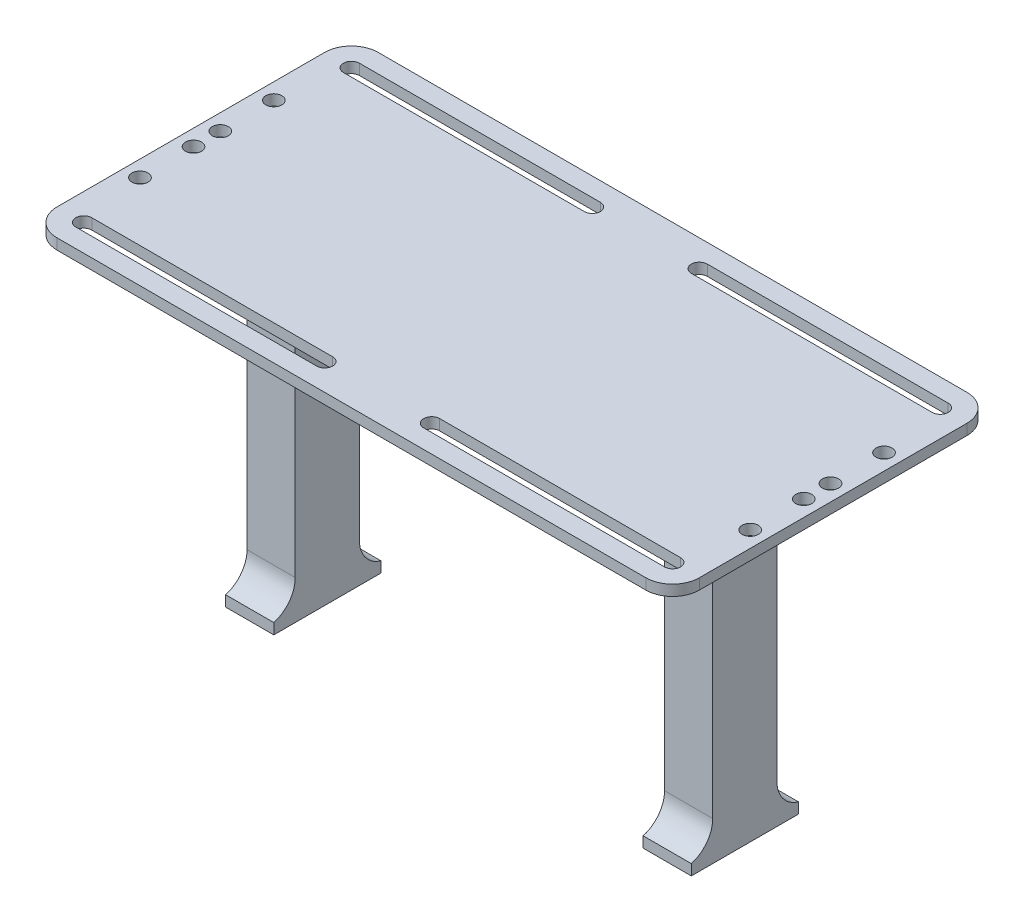
SolidWorks part; units mm, degrees
ref_plane "Front Plane" through (0, 0, 0) normal (0, 0, 1) x (1, 0, 0)
ref_plane "Top Plane" through (0, 0, 0) normal (0, 1, 0) x (1, 0, 0)
ref_plane "Right Plane" through (0, 0, 0) normal (1, 0, 0) x (0, 0, -1)
sketch "Sketch1" plane through (0, 0, 0) normal (0, 1, 0) x (1, 0, 0)
  line L0 (0, -1.9979) -> (0, 3.4727) construction
  line L1 (43.5, -6) -> (34.5, -6)
  line L2 (-43.5, 6) -> (-34.5, 6)
  line L3 (-43.5, 6) -> (-43.5, -6)
  line L4 (-43.5, -6) -> (-34.5, -6)
  line L5 (-34.5, 6) -> (-34.5, -6)
  line L6 (-43.5, 6) -> (-34.5, -6) construction
  line L7 (-43.5, -6) -> (-34.5, 6) construction
  line L8 (34.5, 6) -> (34.5, -6)
  line L9 (43.5, 6) -> (34.5, 6)
  line L10 (43.5, 6) -> (43.5, -6)
  circle A0 centre (-39, 0) radius 1.4
  circle A1 centre (39, 0) radius 1.4
  dimension "D1" = 2.8
  dimension "D2" = 78
  dimension "D3" = 9
  dimension "D4" = 12
extrude "Boss-Extrude1" add sketch "Sketch1" along normal blind 60 contours L3 L2 L5 L4 | L1 L8 L9 L10
sketch "Sketch2" plane through (0, 0, 0) normal (0, -1, 0) x (1, 0, 0)
  line L0 (0, 0) -> (0, 22.5272) construction
  line L1 (-43.5, 10) -> (-34.5, 10)
  line L2 (-43.5, 10) -> (-43.5, -10)
  line L3 (-43.5, -10) -> (-34.5, -10)
  line L4 (-34.5, 10) -> (-34.5, -10)
  line L5 (-34.5, -6) -> (-34.5, 6) construction
  line L6 (-43.5, -6) -> (-43.5, 6) construction
  line L7 (0, 0) -> (5.7315, 0) construction
  line L8 (43.5, -10) -> (34.5, -10)
  line L9 (34.5, 10) -> (34.5, -10)
  line L10 (43.5, 10) -> (34.5, 10)
  line L11 (43.5, 10) -> (43.5, -10)
  point P12 (-34.5, 0)
  dimension "D1" = 20
extrude "Boss-Extrude2" add sketch "Sketch2" along normal blind 2
sketch "Sketch3" plane through (0, -2, 0) normal (0, -1, 0) x (1, 0, 0)
  line L4 (-43.5, -6) -> (-34.5, -6)
  line L5 (-34.5, -6) -> (-34.5, 6)
  line L6 (-34.5, 6) -> (-43.5, 6)
  line L7 (-43.5, 6) -> (-43.5, -6)
  line L8 (-43.5, -6) -> (-34.5, -6)
  line L9 (-34.5, -6) -> (-34.5, 6)
  line L10 (-34.5, 6) -> (-43.5, 6)
  line L11 (-43.5, 6) -> (-43.5, -6)
  line L12 (43.5, 6) -> (34.5, 6)
  line L13 (34.5, 6) -> (34.5, -6)
  line L14 (34.5, -6) -> (43.5, -6)
  line L15 (43.5, -6) -> (43.5, 6)
  line L16 (43.5, 6) -> (34.5, 6)
  line L17 (34.5, 6) -> (34.5, -6)
  line L18 (34.5, -6) -> (43.5, -6)
  line L19 (43.5, -6) -> (43.5, 6)
  circle A1 centre (39, 0) radius 1.4
  circle A2 centre (39, 0) radius 1.4
  circle A3 centre (-39, 0) radius 1.4
  circle A4 centre (-39, 0) radius 1.4
  dimension "D1" = 0
  dimension "D2" = 0
  dimension "D3" = 0
  dimension "D4" = 0
extrude "Cut-Extrude1" cut sketch "Sketch3" against normal blind 6 contours A4 | A2
fillet "Fillet1" radius 5.5 2 edges at (-39, 0, -6) (-39, 0, 6)
fillet "Fillet2" radius 5.5 2 edges at (39, 0, -6) (39, 0, 6)
sketch "Sketch4" plane through (0, 60, 0) normal (0, 1, 0) x (1, 0, 0)
  line L0 (-60, 0) -> (60, 0) construction
  line L1 (-55, 30) -> (55, 30)
  line L2 (-60, 25) -> (-60, -25)
  line L3 (-55, -30) -> (55, -30)
  line L4 (60, 25) -> (60, -25)
  line L5 (-60, 30) -> (60, -30) construction
  line L6 (-60, -30) -> (60, 30) construction
  line L7 (0, -30) -> (0, 30) construction
  line L8 (55, 25) -> (10, 25) construction
  line L11 (55, 23.5) -> (10, 23.5)
  line L14 (-55, -25) -> (-10, -25) construction
  line L15 (-55, -23.5) -> (-10, -23.5)
  line L16 (-55, -26.5) -> (-10, -26.5)
  line L17 (55, 26.5) -> (10, 26.5)
  line L20 (-60, 30) -> (60, -30) construction
  line L21 (-60, -30) -> (60, 30) construction
  line L22 (-55, 30) -> (55, 30)
  line L23 (55, -25) -> (10, -25) construction
  line L26 (-55, 25) -> (-10, 25) construction
  line L27 (-55, 23.5) -> (-10, 23.5)
  line L28 (-55, 26.5) -> (-10, 26.5)
  line L29 (55, -23.5) -> (10, -23.5)
  line L30 (55, -26.5) -> (10, -26.5)
  arc A0 (55, 30) -> (60, 25) centre (55, 25) cw
  arc A1 (-60, -25) -> (-55, -30) centre (-55, -25) ccw
  arc A2 (-55, 30) -> (-60, 25) centre (-55, 25) ccw
  arc A3 (55, -30) -> (60, -25) centre (55, -25) ccw
  arc A8 (-55, -23.5) -> (-55, -26.5) centre (-55, -25) ccw
  arc A9 (-10, -26.5) -> (-10, -23.5) centre (-10, -25) ccw
  circle A10 centre (-57, -2.5) radius 1.5
  circle A11 centre (-57, -12.5) radius 1.5
  circle A16 centre (57, -12.5) radius 1.5
  circle A17 centre (57, -2.5) radius 1.5
  circle A18 centre (57, 2.5) radius 1.5
  circle A19 centre (57, 12.5) radius 1.5
  circle A22 centre (-57, 12.5) radius 1.5
  circle A23 centre (-57, 2.5) radius 1.5
  arc A24 (55, 30) -> (60, 25) centre (55, 25) cw
  arc A25 (-60, 25) -> (-55, 30) centre (-55, 25) cw
  arc A28 (-55, 23.5) -> (-55, 26.5) centre (-55, 25) cw
  arc A29 (-10, 26.5) -> (-10, 23.5) centre (-10, 25) cw
  circle A30 centre (-57, -22.5) radius 1.5
  arc A31 (55, 23.5) -> (55, 26.5) centre (55, 25) ccw
  arc A32 (10, 26.5) -> (10, 23.5) centre (10, 25) ccw
  arc A33 (55, -23.5) -> (55, -26.5) centre (55, -25) cw
  arc A34 (10, -26.5) -> (10, -23.5) centre (10, -25) cw
  point P0 (0, 0)
  point P22 (40.5771, -21.7118)
  point P23 (-10.5349, 27.3757)
  point P25 (32.5, 25)
  point P32 (32.5, -25)
  point P39 (-32.5, -25)
  point P85 (-32.5, 25)
  dimension "D3" = 5
  dimension "D4" = 10
  dimension "D9" = 3
  dimension "D10" = 5
  dimension "D1" = 120
  dimension "D2" = 60
  dimension "D5" = 5
  dimension "D6" = 3
  dimension "D8" = 3
  dimension "D13" = 5
extrude "Boss-Extrude4" add sketch "Sketch4" along normal blind 2
fillet "Fillet4" radius 10 4 edges at (39, 60, 6) (39, 60, -6) (-39, 60, -6) (-39, 60, 6)
